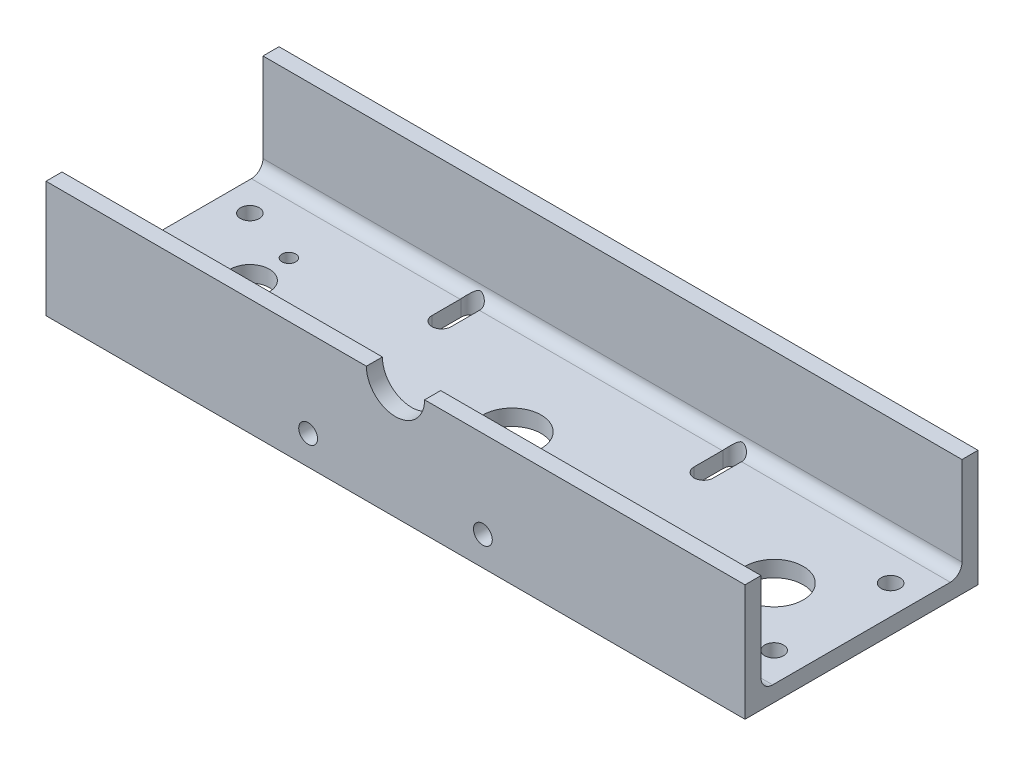
SolidWorks part; units mm, degrees
ref_plane "Front Plane" through (0, 0, 0) normal (0, 0, 1) x (1, 0, 0)
ref_plane "Top Plane" through (0, 0, 0) normal (0, 1, 0) x (1, 0, 0)
ref_plane "Right Plane" through (0, 0, 0) normal (1, 0, 0) x (0, 0, -1)
sketch "Sketch1" plane through (0, 0, 0) normal (1, 0, 0) x (0, 0, -1)
  line L0 (-21.9075, 9.2075) -> (21.9075, 9.2075)
  line L1 (-25.4, -12.7) -> (25.4, -12.7)
  line L2 (-25.4, -12.7) -> (-25.4, 12.7)
  line L3 (-25.4, 12.7) -> (25.4, 12.7)
  line L4 (25.4, -12.7) -> (25.4, 12.7)
  line L5 (-25.4, -12.7) -> (25.4, 12.7) construction
  line L6 (-25.4, 12.7) -> (25.4, -12.7) construction
  line L7 (21.9075, -6.6675) -> (21.9075, 9.2075)
  line L8 (-19.3675, -9.2075) -> (19.3675, -9.2075)
  line L9 (-21.9075, -6.6675) -> (-21.9075, 9.2075)
  line L10 (-21.9075, 9.2075) -> (-21.9075, 12.7)
  line L11 (21.9075, 9.2075) -> (21.9075, 12.7)
  line L12 (21.9075, -9.2075) -> (21.9075, 9.2075) construction
  line L13 (-21.9075, -9.2075) -> (21.9075, -9.2075) construction
  line L14 (-21.9075, -9.2075) -> (-21.9075, 9.2075) construction
  arc A0 (21.9075, -6.6675) -> (19.3675, -9.2075) centre (19.3675, -6.6675) cw
  arc A1 (-19.3675, -9.2075) -> (-21.9075, -6.6675) centre (-19.3675, -6.6675) cw
  point P0 (0, 0)
  dimension "D4" = 2.54
  dimension "D1" = 25.4
  dimension "D2" = 50.8
  dimension "D3" = 3.4925
extrude "Boss-Extrude1" add sketch "Sketch1" along normal blind 152.4 contours L8 A1 L9 L10 L3 L2 L1 L4 L11 L7 A0 region at (0, 1.27, 22.4755)
sketch "Sketch2" plane through (0, -12.7, 0) normal (0, -1, 0) x (1, 0, 0)
  line L0 (0, 0) -> (152.4, 0) construction
  line L3 (0, 25.4) -> (0, -25.4) construction
  line L4 (152.4, 25.4) -> (152.4, -25.4) construction
  line L11 (0, 0) -> (19.05, 0)
  line L12 (152.4, 0) -> (133.35, 0)
  line L13 (19.05, 8.5) -> (19.05, -8.5) construction
  circle A4 centre (19.05, 0) radius 4.25
  circle A5 centre (133.35, 0) radius 6.35
  circle A6 centre (19.05, 8.5) radius 1.5
  circle A7 centre (19.05, -8.5) radius 1.5
  circle A8 centre (76.2, 0) radius 6.35
  dimension "D5" = 17
  dimension "D2" = 8.5
  dimension "D4" = 12.7
  dimension "D6" = 3
  dimension "D7" = 3
  dimension "D8" = 12.7
  dimension "D1" = 19.05
  dimension "D3" = 19.05
sketch "Sketch3" plane through (0, -12.7, 0) normal (0, -1, 0) x (1, 0, 0)
  line L0 (19.05, 0) -> (41.0012, 0) construction
  line L1 (41.0012, 0) -> (54.2488, 0) construction
  line L2 (47.625, 0) -> (47.625, 16.3974) construction
  line L3 (47.625, 19.5724) -> (47.625, 13.2224) construction
  line L4 (49.725, 19.5724) -> (49.725, 13.2224)
  line L5 (45.525, 19.5724) -> (45.525, 13.2224)
  line L6 (76.2, 0) -> (76.2, 25.4) construction
  line L8 (152.4, 25.4) -> (0, 25.4) construction
  line L9 (47.625, 16.3974) -> (76.2, 16.3974) construction
  line L10 (76.2, 0) -> (76.2, -25.4) construction
  line L13 (152.4, -25.4) -> (0, -25.4) construction
  line L16 (47.625, -19.5724) -> (47.625, -13.2224) construction
  line L17 (49.725, -19.5724) -> (49.725, -13.2224)
  line L18 (45.525, -19.5724) -> (45.525, -13.2224)
  line L19 (47.625, -16.3974) -> (76.2, -16.3974) construction
  line L20 (104.775, -19.5724) -> (104.775, -13.2224) construction
  line L21 (102.675, -19.5724) -> (102.675, -13.2224)
  line L22 (106.875, -19.5724) -> (106.875, -13.2224)
  line L23 (104.775, 19.5724) -> (104.775, 13.2224) construction
  line L24 (102.675, 19.5724) -> (102.675, 13.2224)
  line L25 (106.875, 19.5724) -> (106.875, 13.2224)
  circle A0 centre (19.05, 0) radius 21.9512 construction
  arc A3 (26.5537, 20.6288) -> (75.3212, 20.5671) centre (51.0227, 87.8976) ccw construction
  circle A4 centre (47.625, 16.3974) radius 2.1
  arc A5 (49.725, 19.5724) -> (45.525, 19.5724) centre (47.625, 19.5724) ccw
  arc A6 (45.525, 13.2224) -> (49.725, 13.2224) centre (47.625, 13.2224) ccw
  arc A7 (102.675, -19.5724) -> (106.875, -19.5724) centre (104.775, -19.5724) ccw
  arc A12 (49.725, -19.5724) -> (45.525, -19.5724) centre (47.625, -19.5724) cw
  arc A13 (45.525, -13.2224) -> (49.725, -13.2224) centre (47.625, -13.2224) cw
  arc A14 (106.875, -13.2224) -> (102.675, -13.2224) centre (104.775, -13.2224) ccw
  arc A15 (102.675, 19.5724) -> (106.875, 19.5724) centre (104.775, 19.5724) cw
  arc A16 (106.875, 13.2224) -> (102.675, 13.2224) centre (104.775, 13.2224) cw
  point P16 (47.625, 16.3974)
  point P29 (104.775, -16.3974)
  point P36 (104.775, 16.3974)
  point P41 (0, 0)
  point P47 (47.625, -16.3974)
  dimension "D1" = 28.575
  dimension "D2" = 43.9023
  dimension "D3" = 4.2
  dimension "D4" = 2.1
  dimension "D5" = 6.35
  dimension "D6" = 28.575
sketch "Sketch5" plane through (0, -12.7, 0) normal (0, -1, 0) x (1, 0, 0)
  line L0 (0, 25.4) -> (0, -25.4) construction
  line L1 (0, 25.4) -> (6.35, 25.4) construction
  line L2 (0, 25.4) -> (0, 12.7) construction
  line L3 (0, 12.7) -> (6.35, 12.7) construction
  line L4 (6.35, 25.4) -> (6.35, 12.7) construction
  line L5 (152.4, 25.4) -> (0, 25.4) construction
  line L6 (76.2, 0) -> (46.6196, 0)
  line L8 (76.2, 25.4) -> (76.2, 0)
  circle A0 centre (6.35, 12.7) radius 2.05
  circle A7 centre (146.05, 12.7) radius 2.05
  circle A8 centre (146.05, -12.7) radius 2.05
  circle A9 centre (6.35, -12.7) radius 2.05
  dimension "D3" = 4.1
  dimension "D1" = 12.7
  dimension "D2" = 6.35
sketch "Sketch6" plane through (0, 0, 25.4) normal (0, 0, 1) x (1, 0, 0)
  line L0 (76.2, -12.7) -> (76.2, 12.7)
  line L1 (69.85, -12.7) -> (82.55, -12.7) construction
  line L2 (152.4, 12.7) -> (0, 12.7) construction
  circle A0 centre (76.2, 12.7) radius 6.35
  line M5 (152.4, 12.7) -> (0, 12.7)
  dimension "D1" = 12.7
extrude "Cut-Extrude1" cut sketch "Sketch6" against normal blind 9.398 contours A0 L0 M5 | L0 A0 M5 region at (73.505, 10.005, 25.4) region at (78.895, 10.005, 25.4)
extrude "Cut-Extrude2" cut sketch "Sketch5" against normal blind 9.398 contours A0 | A8 | A7 | A9 region at (6.35, -12.7, 12.7) region at (146.05, -12.7, 12.7) region at (146.05, -12.7, -12.7)
extrude "Cut-Extrude3" cut sketch "Sketch2" against normal blind 9.398 contours A4 | A7 | A6 | A8 | A5 region at (19.05, -12.7, -4.1298) region at (127.1796, -12.7, 0) region at (19.05, -12.7, 8.5) region at (19.05, -12.7, -8.5) region at (76.2, -12.7, 0)
extrude "Cut-Extrude4" cut sketch "Sketch3" against normal blind 9.398 contours L4 A5 L5 A4 | A4 | L5 A6 L4 A4 | A13 L18 A12 L17 | L22 A14 L21 A7 | A16 L25 A15 L24 region at (47.625, -12.7, 19.6342) region at (47.625, -12.7, 16.3974) region at (47.625, -12.7, 13.1606) region at (47.625, -12.7, -16.3974) region at (104.775, -12.7, -16.3974) region at (104.775, -12.7, 16.3974)
sketch "Sketch7" plane through (0, 0, 25.4) normal (0, 0, 1) x (1, 0, 0)
  circle A2 centre (95.25, -6.35) radius 2.05
  circle A3 centre (57.15, -6.35) radius 2.05
extrude "Cut-Extrude5" cut sketch "Sketch7" against normal blind 6.35
